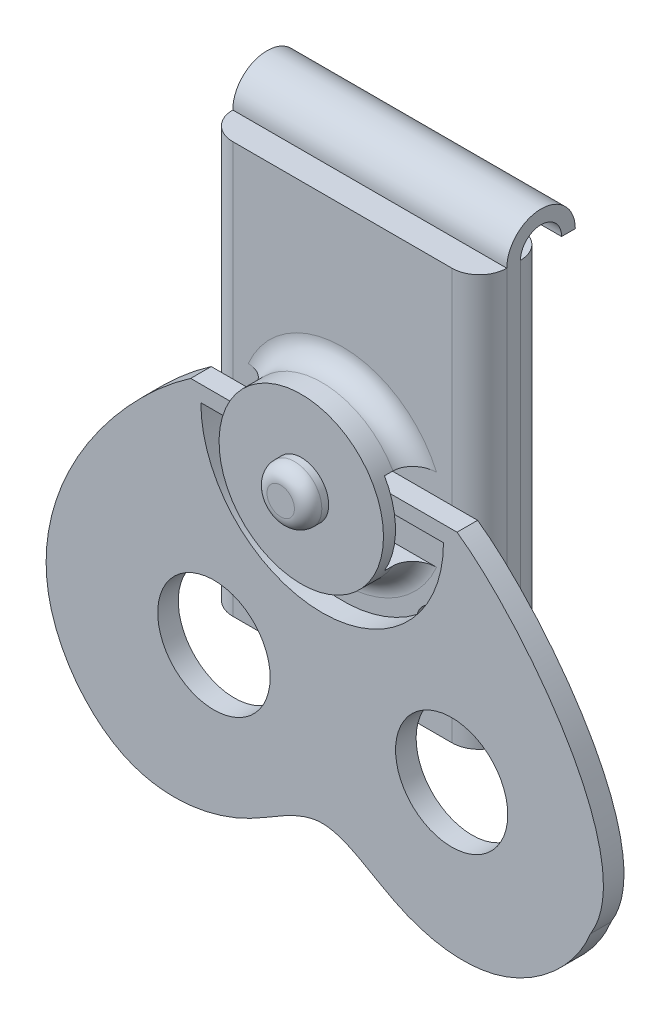
SolidWorks part; units mm, degrees
ref_plane "前视基准面" through (0, 0, 0) normal (0, 0, 1) x (1, 0, 0)
ref_plane "上视基准面" through (0, 0, 0) normal (0, 1, 0) x (1, 0, 0)
ref_plane "右视基准面" through (0, 0, 0) normal (1, 0, 0) x (0, 0, -1)
sketch "草图1" plane through (0, 0, 0) normal (0, 0, 1) x (1, 0, 0)
  line L1 (-10.512, 10.2711) -> (9.488, 10.2711)
  line L2 (-10.512, 10.2711) -> (-10.512, -19.7289)
  line L3 (-10.512, -19.7289) -> (9.488, -19.7289)
  line L4 (9.488, 10.2711) -> (9.488, -19.7289)
  dimension "D1" = 20
  dimension "D2" = 30
extrude "凸台-拉伸1" add sketch "草图1" along normal blind 5
fillet "圆角1" radius 2 4 edges at (9.488, -4.7289, 0) (9.488, -4.7289, 5) (-10.512, -4.7289, 0) (-10.512, -4.7289, 5)
sketch "草图3" plane through (0, 0, 5) normal (0, 0, 1) x (1, 0, 0)
  line L0 (-10.512, -19.7289) -> (-10.512, 10.2711) construction
  circle A0 centre (-0.512, -6.1922) radius 6
  dimension "D1" = 10
  dimension "D2" = 12
extrude "凸台-拉伸2" add sketch "草图3" along normal blind 3
sketch "草图6" plane through (0, 0, 8) normal (0, 0, 1) x (1, 0, 0)
  circle A0 centre (-0.512, -6.1922) radius 2
  dimension "D1" = 4
extrude "凸台-拉伸3" add sketch "草图6" along normal blind 1.5
fillet "圆角2" radius 1 1 edges at (1.488, -6.1922, 9.5)
fillet "圆角3" radius 1.5 1 edges at (5.488, -6.1922, 5)
sketch "草图8" plane through (0, 0, 0) normal (1, 0, 0) x (0, 0, -1)
  line L1 (-7.1235, -3.1922) -> (-5, -3.1922)
  line L3 (-7.1235, -9.1922) -> (-5, -9.1922)
  line L4 (-5, -3.1922) -> (-5, -9.1922)
  line L5 (-5, 1.3078) -> (-5, -13.6922) construction
  line L6 (-8, -4.1922) -> (-8.5, -4.1922) construction
  line L7 (-7.1235, -3.1922) -> (-7.1235, -9.1922)
  dimension "D2" = 1
extrude "切除-拉伸2" cut sketch "草图8" against normal up to next
mirror "镜向1" about plane through (0, 0, 0) normal (1, 0, 0) of "切除-拉伸2"
sketch "草图10" plane through (0, 0, 5) normal (0, 0, 1) x (1, 0, 0)
  line L0 (-9.341, -5.8913) -> (8.3664, -5.8913)
  line L1 (-9.341, -4.7289) -> (9.3556, -4.7289)
  line L2 (-9.341, -4.7289) -> (-10.0829, -4.7289)
  arc A0 (-9.341, -5.8913) -> (8.3664, -5.8913) centre (-0.4873, -5.8913) ccw
  spline S0 degree 3 poles (-10.0829, -4.7289) (-15.4089, -8.376) (-24.9948, -20.2214) (-15.1971, -32.6786) (-6.5875, -31.6264) (-0.4774, -26.6145) (5.4148, -31.4245) (13.2931, -32.2941) (18.0977, -27.7672) (19.0847, -25.2556) knots 0 0 0 0 0.234068 0.319052 0.409666 0.468748 0.528653 0.608526 0.694488 0.694488 0.694488 0.694488
  spline S1 degree 3 poles (9.3556, -4.7289) (13.9925, -7.9454) (22.9721, -19.0961) (19.0847, -25.2556) knots 0 0 0 0 0.887388 0.887388 0.887388 0.887388
extrude "凸台-拉伸4" add sketch "草图10" along normal blind 1.5
sketch "草图11" plane through (0, 0, 6.5) normal (0, 0, 1) x (1, 0, 0)
  circle A0 centre (-8.3858, -20.7339) radius 4.1028
  circle A1 centre (8.9632, -20.7339) radius 4.0939
extrude "切除-拉伸4" cut sketch "草图11" against normal up to surface (1.5 mm away) up to face at (0.2753, -9.7428, 5)
sketch "草图12" plane through (0, 0, 0) normal (0, 0, -1) x (-1, 0, 0)
  line L0 (-7.488, 10.2711) -> (-7.488, -19.7289) construction
  circle A0 centre (-6.488, -13.2986) radius 1.6
  circle A1 centre (7.512, -13.2986) radius 1.6
  dimension "D1" = 3.2
  dimension "D2" = 3.2
  dimension "D3" = 14
  dimension "D4" = 1
extrude "切除-拉伸5" cut sketch "草图12" against normal up to surface (5 mm away) up to face at (-0.5203, -9.0528, 5)
sketch "草图14" plane through (0, 0, 0) normal (1, 0, 0) x (0, 0, -1)
  line L0 (0, 10.2711) -> (-2, 10.2711) construction
  line L1 (-3, 10.2711) -> (-2, 10.2711) construction
  arc A1 (-2.5, 10.2711) -> (1.5, 10.2711) centre (-0.5, 10.2711) cw
  dimension "D1" = 2
sketch "草图15" plane through (0, 10.2711, 0) normal (0, 1, 0) x (1, 0, 0)
  line L1 (-10.512, -2) -> (9.488, -2)
  line L2 (-10.512, -2) -> (-10.512, -3)
  line L3 (-10.512, -3) -> (9.488, -3)
  line L4 (9.488, -2) -> (9.488, -3)
sweep "扫描1" add profiles "草图15" path "草图14"
